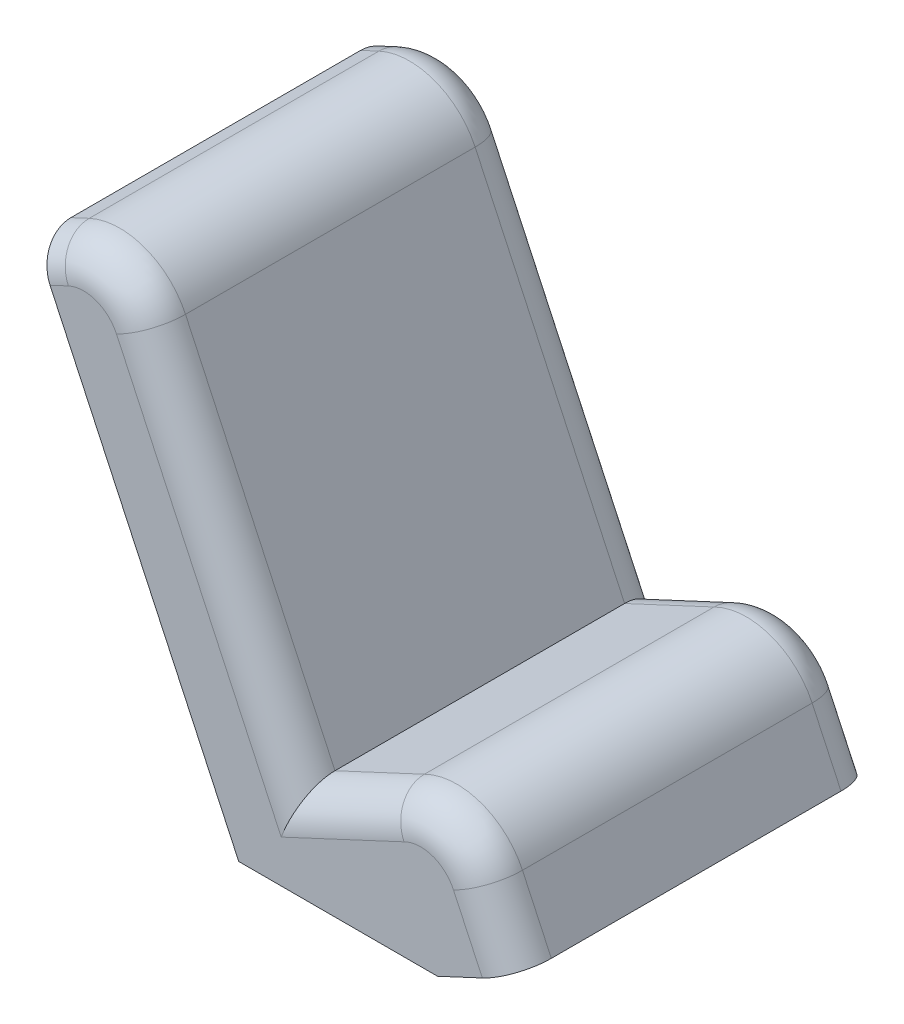
SolidWorks part; units mm, degrees
ref_plane "Front Plane" through (0, 0, 0) normal (0, 0, 1) x (1, 0, 0)
ref_plane "Top Plane" through (0, 0, 0) normal (0, 1, 0) x (1, 0, 0)
ref_plane "Right Plane" through (0, 0, 0) normal (1, 0, 0) x (0, 0, -1)
sketch "Sketch2" plane through (0, 0, 0) normal (0, 0, 1) x (1, 0, 0)
  line L7 (-55.9569, 120) -> (0, 0)
  line L8 (0, 0) -> (57.1, 0)
  line L9 (57.1, 0) -> (78.5451, 10)
  line L10 (78.5451, 10) -> (70.5741, 27.0939)
  line L11 (43.49, 36.5232) -> (18.7784, 25)
  line L12 (18.7784, 25) -> (-22.5046, 113.5315)
  line L14 (-55.9569, 120) -> (-49.0831, 123.2053)
  arc A1 (70.5741, 27.0939) -> (43.49, 36.5232) centre (52.4479, 18.6415) ccw
  arc A2 (-22.5046, 113.5315) -> (-49.0831, 123.2053) centre (-40.6307, 105.0792) ccw
  point P10 (-30.9569, 131.6577)
  dimension "D5" = 10
  dimension "D6" = 20
  dimension "D7" = 20
  dimension "D1" = 120
  dimension "D2" = 25
  dimension "D3" = 155
  dimension "D4" = 57.1
  dimension "D8" = 25
  dimension "D9" = 43.49
extrude "Boss-Extrude1" add sketch "Sketch2" along normal mid plane 100
sketch "Sketch3" plane through (0, 0, 0) normal (0, -1, 0) x (1, 0, 0)
  circle A0 centre (30, 0) radius 7.5
  dimension "D2" = 15
  dimension "D1" = 30
extrude "Boss-Extrude2" add sketch "Sketch3" along normal blind 10
fillet "Fillet1" radius 10 6 edges at (74.5596, 18.5469, 50) (-1.8631, 69.2658, 50) (-52.52, 121.6027, 50) (59.0238, 37.5295, 50) (31.1342, 30.7616, 50) (-33.7903, 123.873, 50)
fillet "Fillet2" radius 10 6 edges at (74.5596, 18.5469, -50) (-1.8631, 69.2658, -50) (-52.52, 121.6027, -50) (59.0238, 37.5295, -50) (31.1342, 30.7616, -50) (-33.7903, 123.873, -50)
chamfer "Chamfer1" distance 2 angle 45 5 edges at (-25.8654, 55.4685, -50) (-54.7191, 117.3455, -47.0711) (-55.9569, 120, 0) (-54.7191, 117.3455, 47.0711) (-25.8654, 55.4685, 50)
